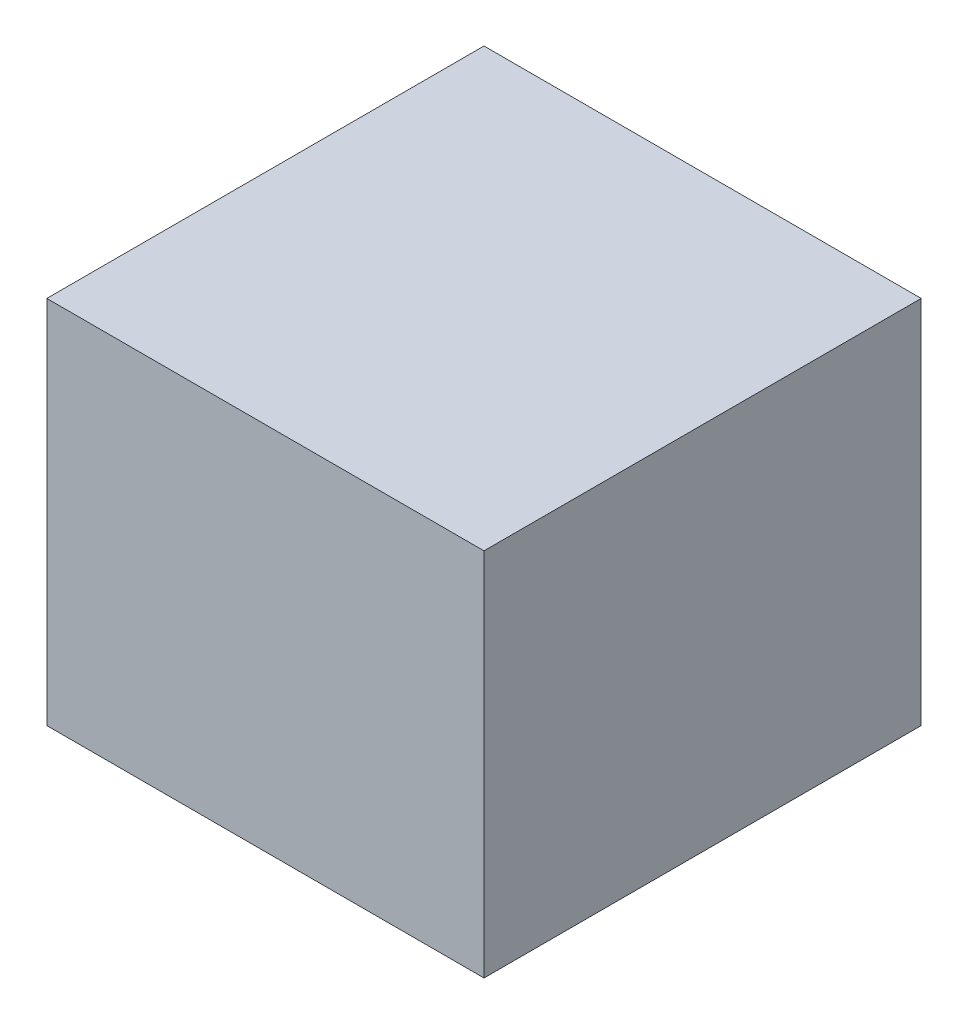
SolidWorks part; units mm, degrees
ref_plane "Front Plane" through (0, 0, 0) normal (0, 0, 1) x (1, 0, 0)
ref_plane "Top Plane" through (0, 0, 0) normal (0, 1, 0) x (1, 0, 0)
ref_plane "Right Plane" through (0, 0, 0) normal (1, 0, 0) x (0, 0, -1)
sketch "Sketch1" plane through (0, 0, 0) normal (0, 1, 0) x (1, 0, 0)
  line L1 (165.1, -165.1) -> (-165.1, -165.1)
  line L2 (165.1, -165.1) -> (165.1, 165.1)
  line L3 (165.1, 165.1) -> (-165.1, 165.1)
  line L4 (-165.1, -165.1) -> (-165.1, 165.1)
  line L5 (165.1, -165.1) -> (-165.1, 165.1) construction
  line L6 (165.1, 165.1) -> (-165.1, -165.1) construction
  point P0 (0, 0)
  dimension "D1" = 330.2
  dimension "D2" = 330.2
extrude "Boss-Extrude1" add sketch "Sketch1" along normal blind 279.4
